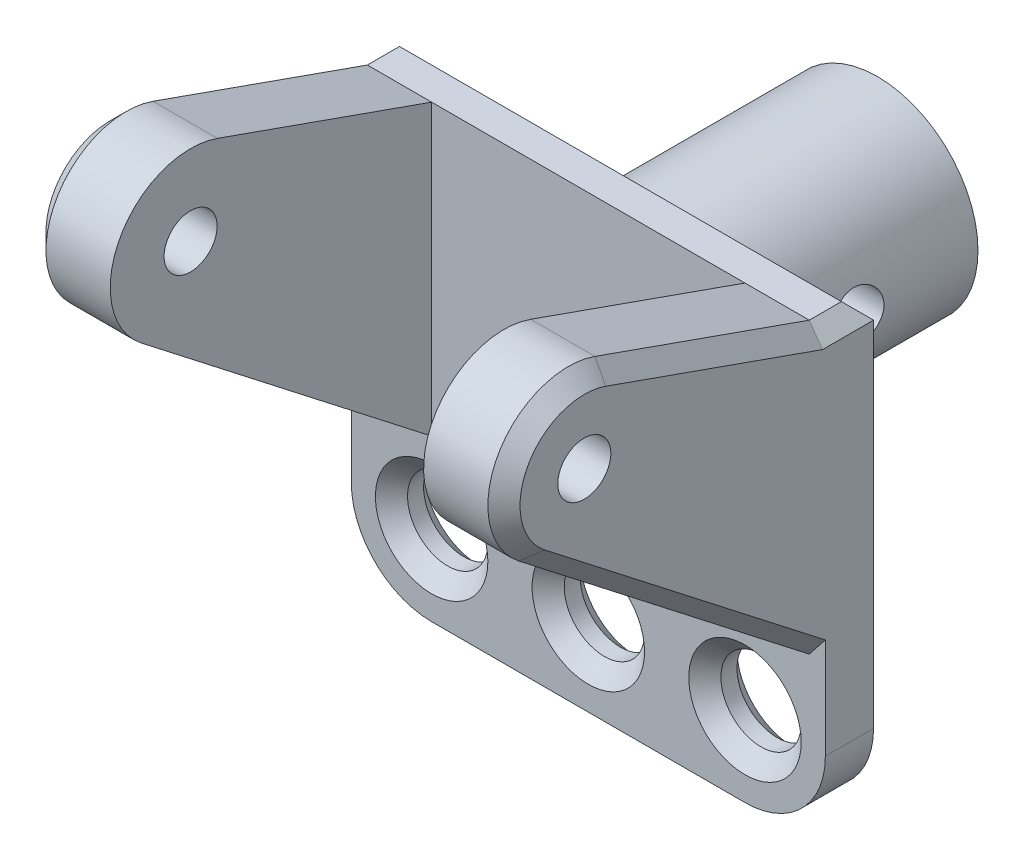
SolidWorks part; units mm, degrees
ref_plane "正面(Front)" through (0, 0, 0) normal (0, 0, 1) x (1, 0, 0)
ref_plane "平面(Top)" through (0, 0, 0) normal (0, 1, 0) x (1, 0, 0)
ref_plane "右側面(Right)" through (0, 0, 0) normal (1, 0, 0) x (0, 0, -1)
sketch "ｽｹｯﾁ1" plane through (0, 0, 0) normal (0, 0, 1) x (1, 0, 0)
  circle A0 centre (0, 0) radius 6.25
  dimension "D1" = 12.5
extrude "ﾎﾞｽ - 押し出し1" add sketch "ｽｹｯﾁ1" along normal blind 15
sketch "ｽｹｯﾁ2" plane through (0, 0, 15) normal (0, 0, 1) x (1, 0, 0)
  line L1 (-14.75, 9) -> (14.75, 9)
  line L2 (-14.75, 9) -> (-14.75, -9)
  line L3 (-14.75, -9) -> (14.75, -9)
  line L4 (14.75, 9) -> (14.75, -9)
  line L5 (-14.75, 9) -> (14.75, -9) construction
  line L6 (-14.75, -9) -> (14.75, 9) construction
  point P0 (0, 0)
  dimension "D1" = 18
  dimension "D2" = 29.5
extrude "ﾎﾞｽ - 押し出し2" add sketch "ｽｹｯﾁ2" along normal blind 3
sketch "ｽｹｯﾁ3" plane through (0, 0, 0) normal (1, 0, 0) x (0, 0, -1)
  line L0 (-18, 9) -> (-31.3333, 13.714)
  line L1 (-36.0696, 5.0531) -> (-18, -9)
  line L2 (-18, 9) -> (-42.4502, 9) construction
  line L4 (-18, 9) -> (-18, -9)
  arc A0 (-31.3333, 13.714) -> (-36.0696, 5.0531) centre (-33, 9) ccw
  circle A1 centre (-33, 9) radius 1.65
  dimension "D2" = 5
  dimension "D3" = 3.3
  dimension "D1" = 15
extrude "ﾎﾞｽ - 押し出し3" add sketch "ｽｹｯﾁ3" against normal blind 5 from surface starting at face at (14.75, 0, 16.5)
extrude "ﾎﾞｽ - 押し出し4" add sketch "ｽｹｯﾁ3<2>" along normal blind 5 from surface starting at face at (-14.75, 0, 16.5)
sketch "ｽｹｯﾁ3<2>" plane through (0, 0, 0) normal (1, 0, 0) x (0, 0, -1) same geometry as "ｽｹｯﾁ3"
sketch "ｽｹｯﾁ4" plane through (0, -9, 0) normal (0, -1, 0) x (1, 0, 0)
  line L6 (-14.75, 15) -> (14.75, 15)
  line L7 (14.75, 15) -> (14.75, 18)
  line L8 (14.75, 18) -> (9.75, 18)
  line L9 (9.75, 18) -> (-9.75, 18)
  line L10 (-9.75, 18) -> (-14.75, 18)
  line L11 (-14.75, 18) -> (-14.75, 15)
  line L12 (-14.75, 15) -> (14.75, 15)
  line L13 (14.75, 15) -> (14.75, 18)
  line L14 (14.75, 18) -> (9.75, 18)
  line L15 (9.75, 18) -> (-9.75, 18)
  line L16 (-9.75, 18) -> (-14.75, 18)
  line L17 (-14.75, 18) -> (-14.75, 15)
  dimension "D1" = 0
extrude "ﾎﾞｽ - 押し出し5" add sketch "ｽｹｯﾁ4" along normal blind 10
fillet "ﾌｨﾚｯﾄ1" radius 5 2 edges at (-14.75, -19, 16.5) (14.75, -19, 16.5)
sketch "ｽｹｯﾁ5" plane through (0, 0, 18) normal (0, 0, 1) x (1, 0, 0)
  line L0 (0, 0) -> (0, -31.2468) construction
  line L1 (9.75, -9) -> (14.75, -9) construction
  line L2 (-9.75, 5.0531) -> (-9.75, -9) construction
  circle A0 centre (0, -14) radius 2.5
  circle A1 centre (-9.75, -14) radius 2.5
  circle A2 centre (9.75, -14) radius 2.5
  dimension "D1" = 5
  dimension "D2" = 5
  dimension "D3" = 5
extrude "ｶｯﾄ - 押し出し1" cut sketch "ｽｹｯﾁ5" against normal through all
chamfer "面取り1" distance 1 angle 45 6 edges at (12.25, -14, 15) (2.5, -14, 15) (-7.25, -14, 15) (-7.25, -14, 18) (2.5, -14, 18) (7.25, -14, 18)
chamfer "面取り2" distance 1 angle 45 9 edges at (-14.75, 9, 16.5) (0, 9, 15) (14.75, 9, 16.5) (-14.75, 11.357, 24.6667) (-14.75, 11.399, 37.3869) (-14.75, -1.9734, 27.0348) (14.75, 11.357, 24.6667) (14.75, 11.399, 37.3869) (14.75, -1.9734, 27.0348)
sketch "ｽｹｯﾁ6" plane through (0, 0, 0) normal (1, 0, 0) x (0, 0, -1)
  line L0 (0, 0) -> (-31.3812, 0) construction
  line L1 (0, -6.25) -> (0, 6.25) construction
  circle A0 centre (-7.5, 0) radius 1.65
  dimension "D1" = 3.3
  dimension "D2" = 7.5
extrude "ｶｯﾄ - 押し出し2" cut sketch "ｽｹｯﾁ6" against normal through all both and the other way through all
